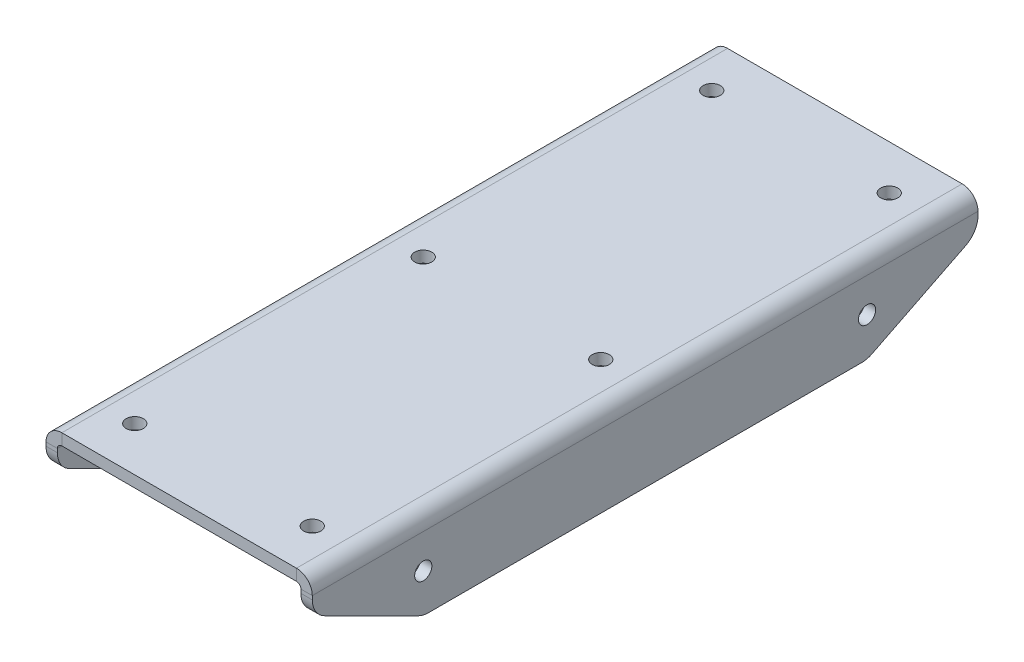
SolidWorks part; units mm, degrees
note: The reader was unsure of these and kept them because the rebuilt part matched: flange length of "Edge-Flange1".
material "5052-H32"
ref_plane "Front Plane" through (0, 0, 0) normal (0, 0, 1) x (1, 0, 0)
ref_plane "Top Plane" through (0, 0, 0) normal (0, 1, 0) x (1, 0, 0)
ref_plane "Right Plane" through (0, 0, 0) normal (1, 0, 0) x (0, 0, -1)
sketch "Sketch1" plane through (0, 0, 0) normal (0, 1, 0) x (1, 0, 0)
  line L1 (-38.1, 95.25) -> (38.1, 95.25)
  line L2 (-38.1, 95.25) -> (-38.1, -95.25)
  line L3 (-38.1, -95.25) -> (38.1, -95.25)
  line L4 (38.1, 95.25) -> (38.1, -95.25)
  line L5 (-38.1, 95.25) -> (38.1, -95.25) construction
  line L6 (-38.1, -95.25) -> (38.1, 95.25) construction
  point P0 (0, 0)
  dimension "D1" = 76.2
  dimension "D2" = 190.5
base flange "Base-Flange1" sketch "Sketch1" thickness 3.2639 reverse thickness direction no parameters "D1"=1.27
edge flange "Edge-Flange1" sketch "Sketch10" flange profiles "Sketch10", "Sketch11" flange angle 90 flange length 25.4 flange position material inside bend radius 1.27 thickness 3.2639 relief rectangular parameters "D1"=2.54, "D6"=10, "D8"=1
sketch "Sketch10" plane through (38.1, -3.2639, 0) normal (-1, 0, 0) x (0, 0, -1)
  line L2 (-95.25, 0) -> (-95.25, 22.1361)
  line L3 (-95.25, 22.1361) -> (95.25, 22.1361)
  line L4 (95.25, 22.1361) -> (95.25, 0)
  line L5 (95.25, 0) -> (-95.25, 0) construction
  line L6 (95.25, 0) -> (-95.25, 0)
sketch "Sketch11" plane through (-38.1, -3.2639, 0) normal (1, 0, 0) x (0, 0, 1)
  line L0 (95.25, 0) -> (-95.25, 0) construction
  line L1 (95.25, 0) -> (-95.25, 0)
  line L2 (95.25, 0) -> (95.25, 22.1361)
  line L3 (95.25, 22.1361) -> (-95.25, 22.1361)
  line L4 (-95.25, 22.1361) -> (-95.25, 0)
bend "EdgeBend1" bend radius 1.27 bend angle 90 parameters "D5"=1
bend "EdgeBend2" bend radius 1.27 bend angle 90 parameters "D5"=2
sketch "Sketch12" plane through (0, 0, 0) normal (0, 1, 0) x (1, 0, 0)
  line L0 (38.1, 95.25) -> (38.1, -95.25) construction
  line L1 (-38.1, 95.25) -> (-38.1, -95.25) construction
  point P0 (-25.4, 82.55)
  point P1 (-25.4, 0)
  point P2 (-25.4, -82.55)
  point P3 (25.4, -82.55)
  point P4 (25.4, 0)
  point P5 (25.4, 82.55)
  dimension "D1" = 12.7
  dimension "D2" = 12.7
  dimension "D3" = 82.55
  dimension "D4" = 82.55
hole_wizard "#10 (0.1935) Diameter Hole1" positions "Sketch13" profile "Sketch14" hole size "#10" standard "ANSI Inch" end condition up to next
sketch "Sketch13" plane through (0, 0, 0) normal (0, 1, 0) x (1, 0, 0)
  point P0 (-25.4, 82.55)
  point P3 (25.4, 82.55)
  point P6 (-25.4, 0)
  point P9 (25.4, 0)
  point P12 (25.4, -82.55)
  point P15 (-25.4, -82.55)
sketch "Sketch14" plane through (-25.4, 0, -82.55) normal (1, 0, 0) x (0, 0, 1)
  line L0 (0, 0) -> (0, 3.2639)
  line L1 (0, 3.2639) -> (2.4574, 3.2639)
  line L2 (2.4574, 3.2639) -> (2.4574, 0)
  line L5 (2.4574, 0) -> (0, 0)
  line L11 (0, -6.35) -> (0, 107.95) construction
  dimension "Thru Hole Dia." = 4.9149
  dimension "Thru Hole Depth" = 3.2639
sketch "Sketch15" plane through (38.1, 0, 0) normal (1, 0, 0) x (0, 0, -1)
  line L0 (-63.5, -14.2875) -> (63.5, -14.2875) construction
  line L1 (-95.25, 0) -> (95.25, 0) construction
  point P0 (-63.5, -14.2875)
  point P1 (63.5, -14.2875)
  point P2 (0, -14.2875)
  dimension "D1" = 14.2875
  dimension "D2" = 127
hole_wizard "#10 (0.1935) Diameter Hole2" positions "Sketch16" profile "Sketch17" hole size "#10" standard "ANSI Inch" end condition through all
sketch "Sketch16" plane through (38.1, 0, 0) normal (1, 0, 0) x (0, 0, -1)
  point P0 (-63.5, -14.2875)
  point P3 (63.5, -14.2875)
sketch "Sketch17" plane through (38.1, -14.2875, 63.5) normal (0, 1, 0) x (0, 0, -1)
  line L0 (0, 0) -> (0, 76.2)
  line L1 (0, 76.2) -> (2.4574, 76.2)
  line L2 (2.4574, 76.2) -> (2.4574, 0)
  line L5 (2.4574, 0) -> (0, 0)
  line L11 (0, -6.35) -> (0, 107.95) construction
  dimension "Thru Hole Dia." = 4.9149
  dimension "Thru Hole Depth" = 76.2
sketch "Sketch19" plane through (38.1, 0, 0) normal (1, 0, 0) x (0, 0, -1)
  line L0 (-95.25, -9.525) -> (-63.5, -25.4)
  line L1 (-95.25, -25.4) -> (-95.25, -4.5339) construction
  line L2 (95.25, -25.4) -> (-95.25, -25.4) construction
  line L3 (-63.5, -25.4) -> (-95.25, -25.4)
  line L4 (-95.25, -25.4) -> (-95.25, -9.525)
  line L5 (-95.25, 0) -> (95.25, 0) construction
  line L6 (0, 0) -> (0, -25.4) construction
  line L7 (63.5, -25.4) -> (95.25, -25.4)
  line L8 (95.25, -9.525) -> (63.5, -25.4)
  line L9 (95.25, -25.4) -> (95.25, -9.525)
  dimension "D1" = 9.525
  dimension "D2" = 31.75
extrude "Cut-Extrude1" cut sketch "Sketch19" against normal through all normal cut yes
fillet "Fillet2" radius 6.35 8 edges at (-36.4681, -9.525, -95.25) (-36.4681, -25.4, -63.5) (36.4681, -9.525, -95.25) (36.4681, -25.4, -63.5) (36.4681, -25.4, 63.5) (36.4681, -9.525, 95.25) (-36.4681, -25.4, 63.5) (-36.4681, -9.525, 95.25)
sketch "Bend-Lines1" [suppressed] plane through (0, 0, 0) normal (0, 1, 0) x (1, 0, 0)
sketch "Bounding-Box1" [suppressed] plane through (0, 0, 0) normal (0, 1, 0) x (1, 0, 0)
sheet metal parameters "Sheet-Metal1" thickness 3.2639 parameters "D1"=2.54
flat pattern "Flat-Pattern1" [suppressed]
sketch "Bend-Lines2" plane through (0, 0, 0) normal (0, 1, 0) x (1, 0, 0)
sketch3d "Bounding-Box2" [suppressed]
  line L0 (34.925, 95.25, 0) -> (34.925, -95.25, 0) construction
  line L1 (-34.925, 95.25, 0) -> (-34.925, -95.25, 0) construction
  line L2 (34.925, 95.25, 0) -> (-34.925, 95.25, 0) construction
  line L3 (34.925, -95.25, 0) -> (-34.925, -95.25, 0) construction
sheet metal parameters "Sheet-Metal2" thickness 3.2639 parameters "D1"=2.54
flat pattern "Flat-Pattern1"
sketch "Bend-Lines2" plane through (0, 0, 0) normal (0, 1, 0) x (1, 0, 0)
  line L0 (-32.6703, 95.25) -> (-32.6703, -95.25) construction
  line L1 (32.6703, -95.25) -> (32.6703, 95.25) construction
  line L2 (-32.6703, 95.25) -> (-32.6703, -95.25) construction
  line L3 (32.6703, -95.25) -> (32.6703, 95.25) construction
sketch3d "Bounding-Box2" [suppressed]
  line L0 (-55.8156, 95.25, 0) -> (-55.8156, -95.25, 0) construction
  line L1 (55.8156, 95.25, 0) -> (55.8156, -95.25, 0) construction
  line L2 (-55.8156, 95.25, 0) -> (55.8156, 95.25, 0) construction
  line L3 (-55.8156, -95.25, 0) -> (55.8156, -95.25, 0) construction
bend of the flat pattern "Flatten-<EdgeBend1>1"
bend of the flat pattern "Flatten-<EdgeBend2>1"
sheet metal parameters "Sheet-Metal3" thickness 3.2639 parameters "D1"=2.54
flat pattern "Flat-Pattern1"
sketch "Bend-Lines2" plane through (0, 0, 0) normal (0, 1, 0) x (1, 0, 0)
  line L0 (-32.6703, 95.25) -> (-32.6703, -95.25) construction
  line L1 (32.6703, -95.25) -> (32.6703, 95.25) construction
  line L2 (-32.6703, 95.25) -> (-32.6703, -95.25) construction
  line L3 (32.6703, -95.25) -> (32.6703, 95.25) construction
sketch3d "Bounding-Box2" [suppressed]
  line L0 (-55.8156, 95.25, 0) -> (-55.8156, -95.25, 0) construction
  line L1 (55.8156, 95.25, 0) -> (55.8156, -95.25, 0) construction
  line L2 (-55.8156, 95.25, 0) -> (55.8156, 95.25, 0) construction
  line L3 (-55.8156, -95.25, 0) -> (55.8156, -95.25, 0) construction
bend of the flat pattern "Flatten-<EdgeBend1>1"
bend of the flat pattern "Flatten-<EdgeBend2>1"
sheet metal parameters "Sheet-Metal4" thickness 3.2639 parameters "D1"=2.54
flat pattern "Flat-Pattern1" [suppressed]
sketch "Bend-Lines2" plane through (0, 0, 0) normal (0, 1, 0) x (1, 0, 0)
  line L0 (-35.8453, 95.25) -> (-35.8453, -95.25) construction
  line L1 (35.8453, -95.25) -> (35.8453, 95.25) construction
  line L2 (-35.8453, 95.25) -> (-35.8453, -95.25) construction
  line L3 (35.8453, -95.25) -> (35.8453, 95.25) construction
sketch3d "Bounding-Box2" [suppressed]
  line L0 (-58.9906, 95.25, 0) -> (-58.9906, -95.25, 0) construction
  line L1 (58.9906, 95.25, 0) -> (58.9906, -95.25, 0) construction
  line L2 (-58.9906, 95.25, 0) -> (58.9906, 95.25, 0) construction
  line L3 (-58.9906, -95.25, 0) -> (58.9906, -95.25, 0) construction
bend of the flat pattern "Flatten-<EdgeBend1>1"
bend of the flat pattern "Flatten-<EdgeBend2>1"
sketch "Sketch15-1" [suppressed] plane through (33.5906, 0, 0) normal (0, 1, 0) x (0, 0, -1)
  line L0 (-63.5, -14.2875) -> (63.5, -14.2875) construction
  line L1 (-95.25, 0) -> (95.25, 0)
  point P0 (-63.5, -14.2875)
  point P1 (63.5, -14.2875)
  dimension "D1" = 14.2875
  dimension "D2" = 127
sheet metal parameters "Sheet-Metal5" thickness 3.2639 parameters "D1"=2.54
flat pattern "Flat-Pattern1" [suppressed]
sketch "Bend-Lines2" plane through (0, 0, 0) normal (0, 1, 0) x (1, 0, 0)
  line L0 (-35.8453, 95.25) -> (-35.8453, -95.25) construction
  line L1 (35.8453, -95.25) -> (35.8453, 95.25) construction
  line L2 (-35.8453, 95.25) -> (-35.8453, -95.25) construction
  line L3 (35.8453, -95.25) -> (35.8453, 95.25) construction
sketch3d "Bounding-Box2" [suppressed]
  line L0 (58.9906, 95.25, 0) -> (58.9906, -95.25, 0) construction
  line L1 (-58.9906, 95.25, 0) -> (-58.9906, -95.25, 0) construction
  line L2 (58.9906, 95.25, 0) -> (-58.9906, 95.25, 0) construction
  line L3 (58.9906, -95.25, 0) -> (-58.9906, -95.25, 0) construction
bend of the flat pattern "Flatten-<EdgeBend1>1"
bend of the flat pattern "Flatten-<EdgeBend2>1"
sketch "Sketch15-1" plane through (33.5906, 0, 0) normal (0, 1, 0) x (0, 0, -1)
  line L0 (-63.5, -14.2875) -> (63.5, -14.2875) construction
  line L1 (-95.25, 0) -> (95.25, 0) construction
  point P0 (-63.5, -14.2875)
  point P1 (63.5, -14.2875)
  dimension "D1" = 14.2875
  dimension "D2" = 127
